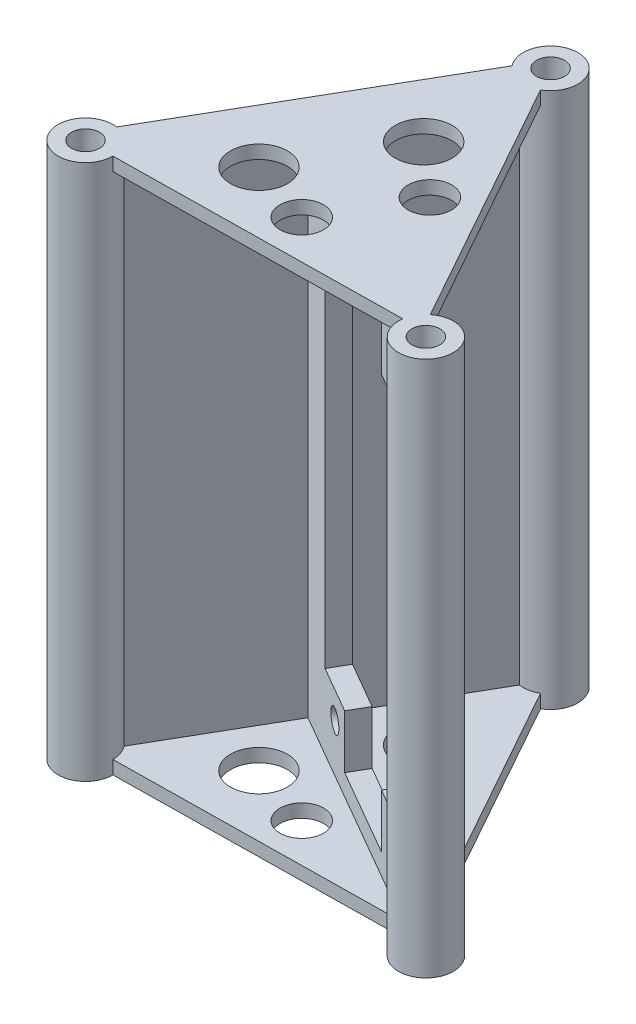
SolidWorks part; units mm, degrees
material "PLA"
ref_plane "Front Plane" through (0, 0, 0) normal (0, 0, 1) x (1, 0, 0)
ref_plane "Top Plane" through (0, 0, 0) normal (0, 1, 0) x (1, 0, 0)
ref_plane "Right Plane" through (0, 0, 0) normal (1, 0, 0) x (0, 0, -1)
sketch "Sketch1" plane through (0, 0, 0) normal (0, 1, 0) x (1, 0, 0)
  line L0 (0, 0) -> (0, 38.1)
  circle A0 centre (0, 0) radius 38.1
  circle A1 centre (0, 29.337) radius 1.5875
  circle A2 centre (25.4066, -14.6685) radius 1.5875
  circle A3 centre (-25.4066, -14.6685) radius 1.5875
  point P13 (0, 0)
  dimension "D1" = 76.2
  dimension "D2" = 3.175
  dimension ".345" = 8.763
  dimension "D4" = 3
extrude "Boss-Extrude1" add sketch "Sketch1" along normal blind 10 contours A1 A0 A3 A2 region at (26.1788, 0, -26.1788)
sketch "Sketch2" plane through (0, 10, 0) normal (0, 1, 0) x (1, 0, 0)
  line L0 (-25.4066, -14.6685) -> (0, 29.337)
  line L1 (-12.7033, 7.3342) -> (25.4066, -14.6685)
  line L2 (-24.1075, -15.4185) -> (1.299, 28.587)
  line L3 (-13.4533, 6.0352) -> (24.6566, -15.9675)
  line L4 (-26.7056, -13.9185) -> (-1.299, 30.087)
  line L5 (-11.9533, 8.6333) -> (26.1566, -13.3695)
  circle A0 centre (-25.4066, -14.6685) radius 1.5875
  circle A1 centre (0, 29.337) radius 1.5875
  circle A2 centre (25.4066, -14.6685) radius 1.5875
  circle A3 centre (-25.4066, -14.6685) radius 2.0875
  circle A4 centre (25.4066, -14.6685) radius 2.0875
  circle A5 centre (0, 29.337) radius 2.0875
  circle A6 centre (-25.4066, -14.6685) radius 4.0875
  circle A7 centre (0, 29.337) radius 4.0875
  circle A8 centre (25.4066, -14.6685) radius 4.0875
  dimension "D1" = 1.5
  dimension "D2" = 1.5
  dimension "D3" = 0.5
  dimension "D4" = 2
extrude "Boss-Extrude2" add sketch "Sketch2" along normal blind 80 separate body contours A7 L4 A6 L0 | A6 L2 L3 L0 | L4 A6 L2 A3 | L0 A6 L4 A3 | L2 A6 L0 A3 | L2 A7 L4 A5 | L4 A7 L0 A5 | L0 A7 L2 A5 | A7 L0 L5 L2 | L0 L3 L2 L1 | L5 L0 L1 L2 | A8 L5 L2 L1 | A8 L1 L2 L3 | L5 A8 L1 A4 | L1 A8 L3 A4 | L3 A8 L5 A4 region at (-13.3542, 10, -7.7101) region at (-17.7805, 10, 2.9633) region at (-12.4288, 10, -6.3097) region at (-11.6788, 10, -7.6088) region at (-23.2723, 10, 12.5108) region at (-24.6051, 10, 11.7413) region at (4.8964, 10, 3.694) region at (-6.324, 10, -16.88) region at (5.6473, 10, 2.3934) region at (-21.6564, 10, 13.36) region at (22.4794, 10, 13.867) region at (22.3237, 10, 14.7541) region at (-2.1343, 10, -27.1793) region at (-0.8015, 10, -26.4098) region at (23.2489, 10, 12.5342) region at (-1.3085, 10, -33.0871)
delete or keep bodies "Body-Delete/Keep 1" type delete bodies bodies 101
sketch "Sketch3" plane through (0, 90, 0) normal (0, 1, 0) x (1, 0, 0)
  line L0 (21.3637, -14.0664) -> (-21.3191, -14.6685)
  line L1 (-12.1543, 5.2852) -> (21.3637, -14.0664) construction
  arc A0 (-24.8045, -10.6256) -> (-22.2064, -12.1256) centre (-25.4066, -14.6685) ccw construction
rib "Rib1" sketch "Sketch3" sketch "Sketch3" thickness 2 extrusion direction parallel to sketch draft on no parameters "D1"=2
sketch "Sketch5" plane through (0, 88, 0) normal (0, -1, 0) x (1, 0, 0)
  line L0 (-22.2064, 12.1256) -> (-12.1543, -5.2852) construction
  line L1 (-12.1543, -5.2852) -> (21.3637, 14.0664) construction
  circle A0 centre (-8.9761, 5.21) radius 4.25
  circle A1 centre (0.6842, 8.4779) radius 3.25
  dimension "D2" = 8.5
  dimension "D6" = 6.5
  dimension "D1" = 8
  dimension "D3" = 7.5
  dimension "D4" = 5.5
  dimension "D5" = 18
extrude "Cut-Extrude1" cut sketch "Sketch5" against normal up to surface (2 mm away) contours A1 | A0 region at (0.6842, 88, 8.4779) up to face at (25.4066, 90, 16.756)
ref_plane "Plane1" through (0, 0, 0) normal (0.5, 0, -0.866) x (-0.866, 0, -0.5)
ref_plane "Plane2" through (0, 50, 0) normal (0, 1, 0) x (1, 0, 0)
mirror "Mirror1" about plane through (0, 50, 0) normal (0, 1, 0) of "Cut-Extrude1", "Rib1"
mirror "Mirror2" about plane through (0, 0, 0) normal (0.5, 0, -0.866) of "Mirror1"
ref_plane "Plane3" through (0, 50, 0) normal (0, -1, 0) x (-1, 0, 0)
ref_plane "Plane4" through (22.8637, 12, 11.4683) normal (0, -1, 0) x (-1, 0, 0)
sketch "Sketch11" plane through (0.75, 0, -1.299) normal (0.5, 0, -0.866) x (-0.866, 0, -0.5)
  line L0 (8.8169, 84.125) -> (13.1685, 84.125) construction
  line L1 (8.8169, 84.125) -> (-21.1831, 84.125)
  line L2 (8.8169, 84.125) -> (8.8169, 15.875)
  line L3 (8.8169, 15.875) -> (-21.1831, 15.875)
  line L4 (-21.1831, 84.125) -> (-21.1831, 15.875)
  line L6 (13.1685, 88) -> (13.1685, 12) construction
  line L7 (8.8169, 84.125) -> (8.8169, 88) construction
  line L8 (13.1685, 88) -> (-25.5347, 88) construction
  line L9 (-21.1831, 84.125) -> (-25.5347, 84.125) construction
  line L10 (-25.5347, 88) -> (-25.5347, 12) construction
  line L11 (8.8169, 15.875) -> (8.8169, 12) construction
  line L12 (-25.5347, 12) -> (13.1685, 12) construction
  dimension "D1" = 68.25
  dimension "D2" = 30
sketch "Sketch12" plane through (-0.75, 0, 1.299) normal (-0.5, 0, 0.866) x (0.866, 0, 0.5)
  line L1 (-2.1971, 80.875) -> (20.8029, 80.875) construction
  line L2 (-2.1971, 80.875) -> (-2.1971, 19.125) construction
  line L3 (-2.1971, 19.125) -> (20.8029, 19.125) construction
  line L4 (20.8029, 80.875) -> (20.8029, 19.125) construction
  line L5 (25.5347, 88) -> (-11.1286, 88) construction
  circle A4 centre (-2.1971, 80.875) radius 1.625
  circle A5 centre (-2.1971, 19.125) radius 1.625
  circle A6 centre (20.8029, 19.125) radius 1.625
  circle A7 centre (20.8029, 80.875) radius 1.625
  dimension "D3" = 3.25
  dimension "D1" = 23
  dimension "D2" = 61.75
  dimension "D4" = 7.125
extrude "Cut-Extrude3" cut sketch "Sketch12" against normal up to surface (3 mm away) up to face at (6.1047, 50, 1.7925)
sketch "Sketch13" plane through (0.75, 0, -1.299) normal (0.5, 0, -0.866) x (-0.866, 0, -0.5)
  line L0 (6.1971, 76.875) -> (6.1971, 23.125)
  line L1 (6.1971, 23.125) -> (-1.8029, 23.125)
  line L2 (-1.8029, 23.125) -> (-1.8029, 15.125)
  line L3 (-1.8029, 15.125) -> (-16.8029, 15.125)
  line L4 (-16.8029, 15.125) -> (-16.8029, 23.125)
  line L5 (-16.8029, 23.125) -> (-24.8029, 23.125)
  line L6 (-24.8029, 23.125) -> (-24.8029, 76.875)
  line L7 (-24.8029, 76.875) -> (-16.8029, 76.875)
  line L8 (-16.8029, 76.875) -> (-16.8029, 84.875)
  line L12 (6.1971, 76.875) -> (-1.8029, 76.875)
  line L13 (-1.8029, 76.875) -> (-1.8029, 84.875)
  line L14 (-1.8029, 84.875) -> (-16.8029, 84.875)
  circle A1 centre (2.1971, 80.875) radius 1.625 construction
  circle A2 centre (-20.8029, 80.875) radius 1.625 construction
  circle A3 centre (2.1971, 19.125) radius 1.625 construction
  dimension "D1" = 4
  dimension "D6" = 4
  dimension "D2" = 4
  dimension "D3" = 4
  dimension "D4" = 4
  dimension "D5" = 4
extrude "Cut-Extrude4" cut sketch "Sketch13" against normal up to surface (3 mm away) up to face at (18.6732, 19.125, 12.513)
